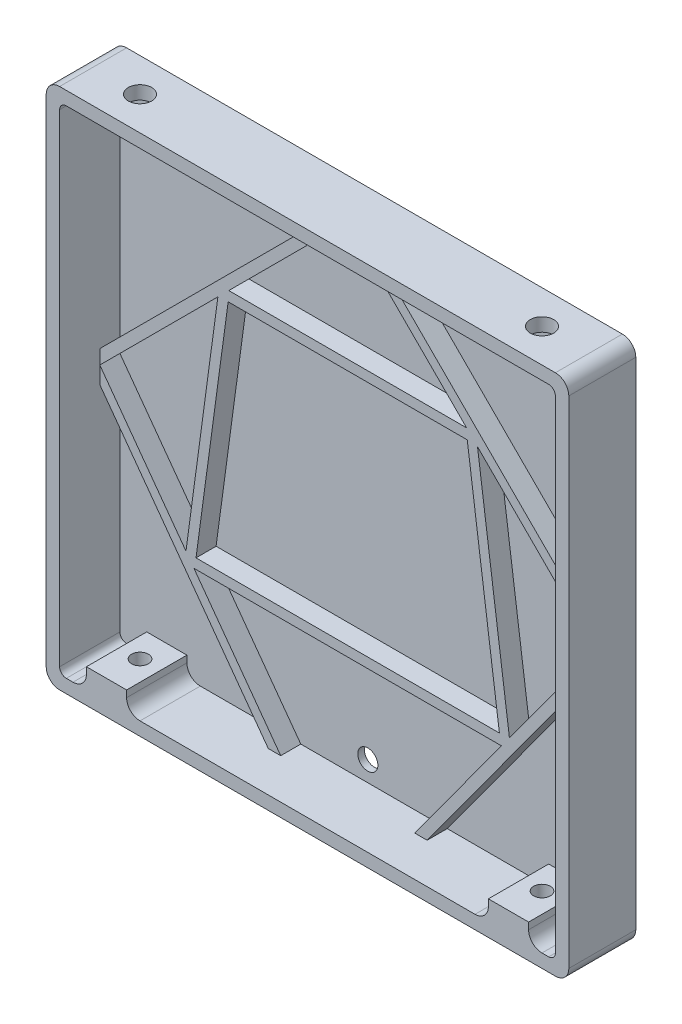
SolidWorks part; units mm, degrees
ref_plane "Front Plane" through (0, 0, 0) normal (0, 0, 1) x (1, 0, 0)
ref_plane "Top Plane" through (0, 0, 0) normal (0, 1, 0) x (1, 0, 0)
ref_plane "Right Plane" through (0, 0, 0) normal (1, 0, 0) x (0, 0, -1)
sketch "Sketch1" plane through (0, 0, 0) normal (0, 0, 1) x (1, 0, 0)
  line L1 (-39, -39) -> (39, -39)
  line L2 (-39, -39) -> (-39, 39)
  line L3 (-39, 39) -> (39, 39)
  line L4 (39, -39) -> (39, 39)
  line L5 (-39, -39) -> (39, 39) construction
  line L6 (-39, 39) -> (39, -39) construction
  point P0 (0, 0)
  dimension "D1" = 78
  dimension "D2" = 78
extrude "Boss-Extrude1" add sketch "Sketch1" along normal blind 10
sketch "Sketch9" plane through (0, 0, 10) normal (0, 0, 1) x (1, 0, 0)
  line L0 (-39, 39) -> (-39, -39) construction
  line L6 (-39, 16) -> (-34, 16)
  line L7 (-39, 16) -> (-39, 14)
  line L8 (-39, 14) -> (-34, 14)
  line L9 (-34, 16) -> (-34, 14)
  point P10 (-39, 15)
  dimension "D1" = 5
  dimension "D2" = 2
  dimension "D3" = 15
extrude "Cut-Extrude6" [suppressed] cut sketch "Sketch9" against normal offset from surface (9 mm away) 1 up to face at (0, 0, 0)
mirror "Mirror3" [suppressed] about plane through (0, 0, 0) normal (0, 1, 0)
ref_axis "Axis1" [suppressed] through (0, 0, 10.5) along (0, 0, -1)
pattern_circular "CirPattern1" [suppressed] count 4 over 360 about axis through (0, 0, 10.5) along (0, 0, -1) of bodies 119
shell "Shell1" thickness 2 removed face at (0, 0, 10)
sketch "Sketch10" plane through (0, 0, 0) normal (0, 1, 0) x (1, 0, 0)
  line L0 (39, 0) -> (-39, 0) construction
  circle A0 centre (-30, -5) radius 1.25
  dimension "D3" = 2.5
  dimension "D1" = 30
  dimension "D2" = 5
extrude "Cut-Extrude7" cut sketch "Sketch10" against normal through all both and the other way through all
mirror "Mirror4" about plane through (0, 0, 0) normal (1, 0, 0) of "Cut-Extrude7"
fillet "Fillet1" [suppressed] radius 1
fillet "Fillet2" [suppressed] radius 2
sketch "Sketch13" plane through (0, 0, 1) normal (0, 0, 1) x (1, 0, 0)
  line L0 (-39, -39) -> (39, -39) construction
  circle A0 centre (0, -34) radius 1.5
  dimension "D1" = 3
  dimension "D2" = 5
extrude "Cut-Extrude8" cut sketch "Sketch13" against normal through all
fillet "Fillet5" radius 2 4 edges at (39, 39, 5) (39, -39, 5) (-39, -39, 5) (-39, 39, 5)
fillet "Fillet6" radius 1 4 edges at (37, 37, 5.5) (-37, 37, 5.5) (-37, -37, 5.5) (37, -37, 5.5)
fillet "Fillet4" [suppressed] radius 1
sketch "Sketch15" plane through (0, -37, 0) normal (0, 1, 0) x (1, 0, 0)
  line L0 (-36, -1) -> (36, -1) construction
  line L1 (-33, -1) -> (-27, -1)
  line L2 (-33, -1) -> (-33, -10)
  line L3 (-33, -10) -> (-27, -10)
  line L4 (-27, -1) -> (-27, -10)
  line L5 (-36, -10) -> (36, -10) construction
  line L6 (-30, -5) -> (-30, -10) construction
  circle A0 centre (-30, -5) radius 1.25 construction
  circle A1 centre (-30, -5) radius 1.25
  dimension "D1" = 6
extrude "Boss-Extrude2" add sketch "Sketch15" along normal blind 3
fillet "Fillet7" radius 2 2 edges at (-27, -37, 5.5) (-33, -37, 5.5)
mirror "Mirror5" about plane through (0, 0, 0) normal (1, 0, 0) of "Fillet7", "Boss-Extrude2"
sketch "Sketch16" plane through (0, 37, 0) normal (0, -1, 0) x (1, 0, 0)
  circle A0 centre (-30, 5) radius 1.75
  circle A1 centre (30, 5) radius 1.75
  dimension "D1" = 3.5
extrude "Cut-Extrude9" cut sketch "Sketch16" against normal through all
sketch "Sketch17" plane through (0, 0, 1) normal (0, 0, 1) x (1, 0, 0)
  line L0 (0, 37) -> (-37, 0)
  line L1 (36, 37) -> (-36, 37) construction
  line L2 (-37, 36) -> (-37, -36) construction
  line L3 (-37, 0) -> (-10, -37)
  line L4 (-25, -37) -> (25, -37) construction
  dimension "D1" = 10
extrude "Extrude-Thin1" add sketch "Sketch17" along normal blind 3 thin thin type one direction wall 1.5
mirror "Mirror6" about plane through (0, 0, 0) normal (1, 0, 0) of "Extrude-Thin1"
sketch "Sketch18" plane through (0, 0, 1) normal (0, 0, 1) x (1, 0, 0)
  line L0 (-18.5, 18.5) -> (18.5, 18.5)
  line L1 (0, 37) -> (-37, 0) construction
  line L2 (0, 37) -> (37, 0) construction
  line L3 (18.5, 18.5) -> (23.5, -18.5)
  line L4 (37, 0) -> (10, -37) construction
  line L5 (23.5, -18.5) -> (-23.5, -18.5)
  line L6 (-37, 0) -> (-10, -37) construction
  line L7 (-23.5, -18.5) -> (-18.5, 18.5)
extrude "Extrude-Thin2" add sketch "Sketch18" along normal up to surface (3 mm away) thin up to face at (-19.0303, 19.0303, 4) thin type mid plane wall 1.5
